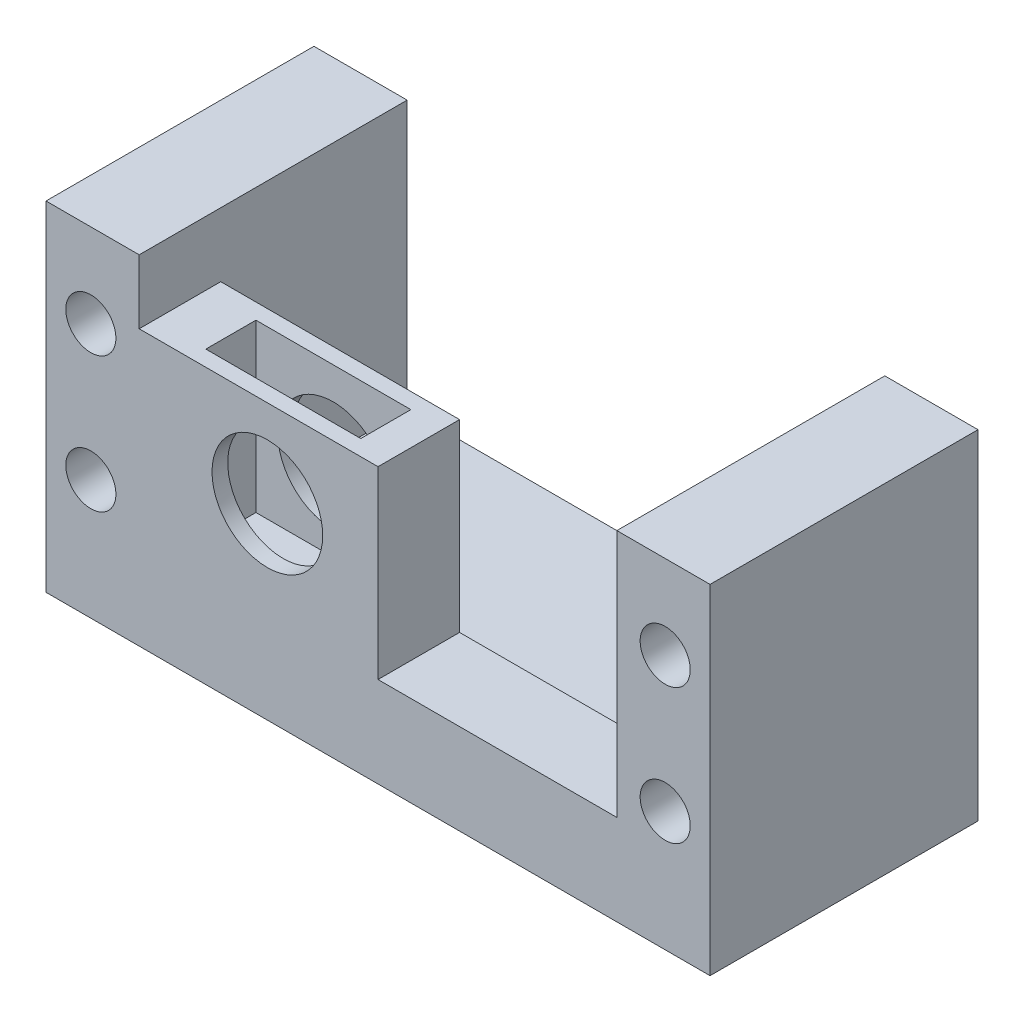
SolidWorks part; units mm, degrees
ref_plane "Спереди" through (0, 0, 0) normal (0, 0, 1) x (1, 0, 0)
ref_plane "Сверху" through (0, 0, 0) normal (0, 1, 0) x (1, 0, 0)
ref_plane "Справа" through (0, 0, 0) normal (1, 0, 0) x (0, 0, -1)
sketch "Эскиз1" plane through (0, 0, 0) normal (0, 0, 1) x (1, 0, 0)
  line L2 (-59.1906, -40.1769) -> (-59.1906, -15.0857)
  line L3 (-59.1906, -15.0857) -> (-51.1906, -15.0857)
  line L4 (-2.1906, -38.0857) -> (-2.1906, -15.0857)
  line L8 (-2.1906, -15.0857) -> (-10.1906, -15.0857)
  line L9 (-10.1906, -15.0857) -> (-10.1906, -38.0857)
  line L10 (-51.1906, -15.0857) -> (-51.1906, -38.0857)
  line L11 (-51.1906, -38.0857) -> (-10.1906, -38.0857)
  line L12 (-59.1906, -40.1769) -> (-59.1906, -44.1769)
  line L13 (-59.1906, -44.1769) -> (-2.1906, -44.1769)
  line L14 (-2.1906, -44.1769) -> (-2.1906, -38.0857)
  point P0 (0, 0)
extrude "Бобышка-Вытянуть1" add sketch "Эскиз1" along normal blind 23
sketch "Эскиз3" plane through (-59.1906, 0, 0) normal (-1, 0, 0) x (0, 0, 1)
  line L5 (0, -15.0857) -> (0, -44.1769) construction
  line L6 (15, -15.0857) -> (0, -15.0857) construction
  line L7 (15, -15.0857) -> (15, -38.2478) construction
  line L8 (15, -38.2478) -> (0, -38.2478) construction
  line L9 (0, -15.0857) -> (0, -38.2478) construction
sketch "Эскиз5" plane through (0, 0, 23) normal (0, 0, 1) x (1, 0, 0)
  line L0 (-51.1906, -38.0857) -> (-51.1906, -15.0857) construction
  line L1 (-10.1906, -28.0857) -> (-24.1906, -28.0857) construction
  line L6 (-30.6906, -18.0857) -> (-30.6906, -34.9839) construction
  line L11 (-51.1906, -28.0857) -> (-37.1906, -28.0857) construction
  line L12 (-10.1906, -38.0857) -> (-51.1906, -38.0857) construction
  line L13 (-10.1906, -38.0857) -> (-10.1906, -18.0857) construction
  line L14 (-10.1906, -18.0857) -> (-51.1906, -18.0857) construction
  line L15 (-51.1906, -38.0857) -> (-51.1906, -18.0857) construction
  line L16 (-21.1906, -34.9839) -> (-51.1906, -34.9839) construction
  line L18 (-21.1906, -20.5857) -> (-51.1906, -20.5857)
  line L19 (-51.1906, -34.9839) -> (-51.1906, -20.5857)
  line L20 (-21.1906, -20.5857) -> (-10.1906, -20.5857)
  line L22 (-21.1906, -34.9839) -> (-10.1906, -34.9839) construction
  line L23 (-10.1906, -20.5857) -> (-10.1906, -34.9839)
  line L24 (-10.1906, -38.0857) -> (-51.1906, -38.0857)
  line L25 (-51.1906, -38.0857) -> (-51.1906, -34.9839)
  line L26 (-10.1906, -38.0857) -> (-10.1906, -34.9839)
  circle A5 centre (-21.1906, -28.0857) radius 2.7
  circle A6 centre (-40.1906, -28.0857) radius 4.75
extrude "Бобышка-Вытянуть6" add sketch "Эскиз5" against normal blind 7
sketch "Эскиз6" plane through (0, 0, 23) normal (0, 0, 1) x (1, 0, 0)
  line L0 (-51.1906, -20.5857) -> (-51.1906, -15.0857) construction
  line L3 (-10.1906, -18.0857) -> (-51.1906, -18.0857)
  line L4 (-51.1906, -38.0857) -> (-51.1906, -18.0857)
  line L5 (-2.1906, -38.0857) -> (-59.1906, -38.0857) construction
  line L6 (-2.1906, -44.1769) -> (-2.1906, -15.0857) construction
  line L7 (-6.0406, -38.0857) -> (-6.0406, -29.5857) construction
  line L8 (-59.1906, -15.0857) -> (-59.1906, -44.1769) construction
  line L9 (-10.1906, -18.0857) -> (-2.1906, -18.0857) construction
  line L10 (-6.0406, -18.0857) -> (-6.0406, -26.5857) construction
  line L11 (-6.0406, -22.2857) -> (-10.1906, -22.2857) construction
  line L12 (-30.6906, -38.0857) -> (-30.6906, -18.0857) construction
  line L13 (-10.1906, -18.0857) -> (-10.1906, -38.0857) construction
  line L14 (-6.0406, -33.8857) -> (-10.1906, -33.8857) construction
  circle A1 centre (-6.0406, -33.8857) radius 2.15
  circle A3 centre (-6.0406, -22.2857) radius 2.15
  circle A4 centre (-55.3406, -22.2857) radius 2.15
  circle A5 centre (-55.3406, -33.8857) radius 2.15
extrude "Вырез-Вытянуть2" cut sketch "Эскиз6" against normal through all contours A1 | A3 | A5 | A4 region at (-6.0406, -33.8857, 23) region at (-6.0406, -22.2857, 23) region at (-55.3406, -22.2857, 23) region at (-55.3406, -33.8857, 23)
sketch "Эскиз8" plane through (0, 0, 23) normal (0, 0, 1) x (1, 0, 0)
  line L1 (-10.1906, -20.5857) -> (-30.6906, -20.5857)
  line L2 (-10.1906, -20.5857) -> (-10.1906, -36.4088)
  line L3 (-10.1906, -36.4088) -> (-30.6906, -36.4088)
  line L4 (-30.6906, -20.5857) -> (-30.6906, -36.4088)
extrude "Вырез-Вытянуть4" cut sketch "Эскиз8" against normal up to surface (7 mm away) up to face at (-44.9406, -28.0857, 16)
sketch "Эскиз10" plane through (0, 0, 16) normal (0, 0, -1) x (-1, 0, 0)
  line L0 (40.1906, -23.3357) -> (40.1906, -20.5857) construction
  line L1 (30.6906, -20.5857) -> (51.1906, -20.5857) construction
  circle A0 centre (40.1906, -28.0857) radius 4.75 construction
sketch "Эскиз11" plane through (0, -20.5857, 0) normal (0, 1, 0) x (1, 0, 0)
  line L0 (-40.1712, -16) -> (-40.1712, -23) construction
  line L1 (-30.6906, -16) -> (-51.1906, -16) construction
  line L2 (-30.6906, -23) -> (-51.1906, -23) construction
  line L4 (-46.8212, -21.65) -> (-33.5212, -21.65)
  line L5 (-46.8212, -21.65) -> (-46.8212, -17.35)
  line L6 (-46.8212, -17.35) -> (-33.5212, -17.35)
  line L7 (-33.5212, -21.65) -> (-33.5212, -17.35)
  line L8 (-46.8212, -21.65) -> (-33.5212, -17.35) construction
  line L9 (-46.8212, -17.35) -> (-33.5212, -21.65) construction
  point P6 (-40.1712, -19.5)
  point P11 (0, 0)
  point P12 (0, 0)
extrude "Вырез-Вытянуть6" cut sketch "Эскиз11" against normal blind 14.3
sketch "Эскиз12" plane through (0, 0, 16) normal (0, 0, -1) x (-1, 0, 0)
  line L0 (41.6581, -20.5857) -> (41.6581, -27.5857) construction
  line L1 (40.1906, -34.5857) -> (40.1906, -20.5857) construction
  line L2 (30.6906, -20.5857) -> (51.1906, -20.5857) construction
  line L3 (40.1906, -21.5857) -> (40.1906, -34.5857)
  point P8 (40.1906, -28.0857)
